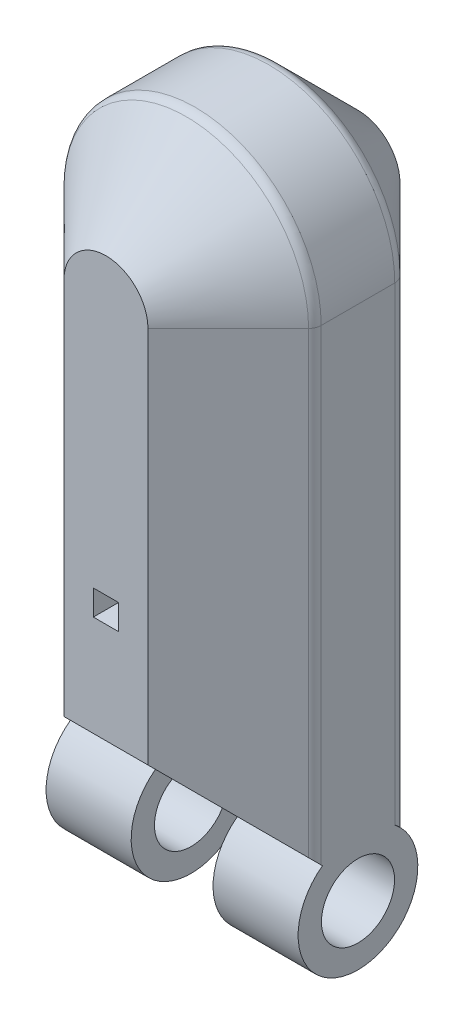
SolidWorks part; units mm, degrees
ref_plane "Front Plane" through (0, 0, 0) normal (0, 0, 1) x (1, 0, 0)
ref_plane "Top Plane" through (0, 0, 0) normal (0, 1, 0) x (1, 0, 0)
ref_plane "Right Plane" through (0, 0, 0) normal (1, 0, 0) x (0, 0, -1)
sketch "Sketch1" plane through (0, 0, 0) normal (0, 1, 0) x (1, 0, 0)
  line L0 (-1.6667, -5) -> (1.6667, -5)
  line L1 (1.6667, -5) -> (5, -1.6667)
  line L2 (5, -1.6667) -> (5, 1.6667)
  line L3 (5, 1.6667) -> (1.6667, 5)
  line L4 (1.6667, 5) -> (-1.6667, 5)
  line L5 (-1.6667, 5) -> (-5, 1.6667)
  line L6 (-5, 1.6667) -> (-5, -1.6667)
  line L7 (-5, -1.6667) -> (-1.6667, -5)
  point P2 (-23.4035, -6.4439)
  point P9 (0, 0)
  point P10 (0, 0)
  point P11 (0, 0)
  point P12 (0, 0)
  point P13 (-20.4677, -7.9197)
  point P14 (-21.0793, -7.5528)
  point P15 (-3.1432, 6.2245)
  point P16 (5, 0)
  point P18 (5.7476, -2.7846)
  point P19 (0, -5)
  point P20 (2.8311, 7.5)
  dimension "D1" = 135
  dimension "D2" = 10
  dimension "D3" = 10
  dimension "D4" = 3.3333
extrude "Boss-Extrude1" add sketch "Sketch1" along normal blind 20
sketch "Sketch2" plane through (0, 0, 0) normal (1, 0, 0) x (0, 0, -1)
  line L3 (-5, 20) -> (-5, 0) construction
  line L5 (0, 0) -> (-5, 0)
  line L6 (-1.6667, 0) -> (1.6667, 0) construction
  line L7 (-5, 0) -> (-5, 5)
  line L8 (-5, 5) -> (0, 0)
  dimension "D2" = 45
extrude "Cut-Extrude1" cut sketch "Sketch2" against normal through all both and the other way through all contours L8 L5 L7
sketch "Sketch3" plane through (0, 0, 0) normal (0, 1, 0) x (1, 0, 0)
  line L0 (0, -4) -> (-0.5, -3.5)
  line L1 (-0.5, -3.5) -> (-0.5, -3)
  line L2 (-0.5, -3) -> (0.5, -3)
  line L3 (0.5, -3) -> (0.5, -3.5)
  line L4 (0.5, -3.5) -> (0, -4)
  line L6 (0.5, 4) -> (0.5, 3.5)
  line L7 (-0.5, 4) -> (0.5, 4)
  line L8 (-0.5, 3.5) -> (-0.5, 4)
  line L9 (0, 3) -> (-0.5, 3.5)
  line L10 (0.5, 3.5) -> (0, 3)
  line L11 (1.6667, 5) -> (-1.6667, 5) construction
  line L12 (-1.6667, -5) -> (1.6667, -5) construction
  point P2 (0.5, 4.6041)
  point P6 (0, -3)
  point P13 (0, -5)
  dimension "D1" = 1
  dimension "D2" = 0.5
  dimension "D3" = 0.5
  dimension "D4" = 0.5
  dimension "D5" = 1
  dimension "D6" = 2
  dimension "D7" = 1
extrude "Cut-Extrude2" cut sketch "Sketch3" along normal blind 10
sketch "Sketch6" plane through (0, 0, 0) normal (1, 0, 0) x (0, 0, -1)
  circle A0 centre (0, -0.5) radius 2.625
  dimension "D2" = 5.25
  dimension "D1" = 0.5
extrude "Cut-Extrude4" cut sketch "Sketch6" against normal mid plane 3.25
sketch "Sketch7" plane through (-1.625, 0, 0) normal (1, 0, 0) x (0, 0, -1)
  circle A0 centre (0, -0.5) radius 2.375
  dimension "D2" = 4.75
  dimension "D1" = 0.5
extrude "Boss-Extrude3" add sketch "Sketch7" against normal up to surface (3.375 mm away) up to face at (-5, 8.3333, 0)
sketch "Sketch8" plane through (1.625, 0, 0) normal (-1, 0, 0) x (0, 0, 1)
  circle A0 centre (0, -0.5) radius 2.375
  dimension "D2" = 4.75
  dimension "D1" = 0.5
extrude "Boss-Extrude4" add sketch "Sketch8" against normal up to surface (3.375 mm away) up to face at (5, 8.3333, 0)
sketch "Sketch11" plane through (5, 0, 0) normal (1, 0, 0) x (0, 0, -1)
  circle A0 centre (0, -0.5) radius 1.45
  dimension "D1" = 2.9
extrude "Cut-Extrude6" cut sketch "Sketch11" against normal through all both and the other way through all
sketch "Sketch12" plane through (0, 20, 0) normal (0, 1, 0) x (1, 0, 0)
  line L0 (0, 5) -> (-1.6667, 5)
  line L1 (1.6667, 5) -> (-1.6667, 5) construction
  line L2 (-1.6667, 5) -> (-5, 1.6667)
  line L3 (-5, 1.6667) -> (-5, -1.6667)
  line L4 (-5, -1.6667) -> (-1.6667, -5)
  line L5 (-1.6667, -5) -> (0, -5)
  line L6 (-1.6667, -5) -> (1.6667, -5) construction
  line L7 (0, -5) -> (0, 5)
revolve "Revolve1" add sketch "Sketch12" angle 180 about L7
fillet "Fillet1" radius 0.5 3 edges at (5, 10.8333, 1.6667) (-5, 10.8333, 1.6667) (0, 25, 1.6667)
fillet "Fillet2" radius 0.5 3 edges at (5, 10.596, -1.6667) (-5, 10.596, -1.6667) (0, 25, -1.6667)
sketch "Sketch13" plane through (0, 0, 3) normal (0, 0, 1) x (1, 0, 0)
  line L0 (0.5, 10) -> (-0.5, 10) construction
  line L1 (0.5, 10) -> (-0.5, 10)
  line L2 (0.5, 10) -> (0.5, 9)
  line L3 (0.5, 9) -> (-0.5, 9)
  line L4 (-0.5, 10) -> (-0.5, 9)
  point P4 (0, 9)
  dimension "D1" = 1
  dimension "D2" = 1
extrude "Cut-Extrude7" cut sketch "Sketch13" along normal through all
sketch "Sketch14" plane through (0, 0, -4) normal (0, 0, 1) x (1, 0, 0)
  line L0 (0.5, 10) -> (-0.5, 10) construction
  line L1 (0.5, 9) -> (-0.5, 9)
  line L2 (0.5, 9) -> (0.5, 10)
  line L3 (0.5, 10) -> (-0.5, 10)
  line L4 (-0.5, 9) -> (-0.5, 10)
  point P4 (0, 9)
  dimension "D1" = 1
  dimension "D2" = 1
extrude "Cut-Extrude8" cut sketch "Sketch14" against normal through all
